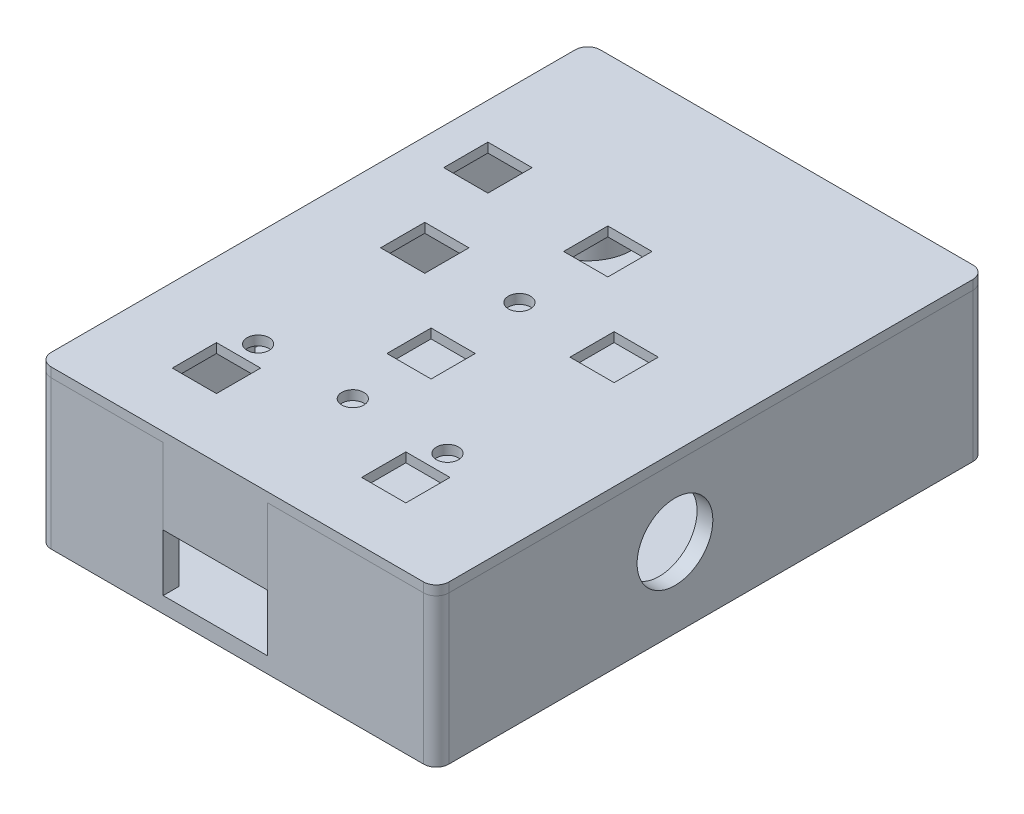
SolidWorks part; units mm, degrees
ref_plane "前视基准面" through (0, 0, 0) normal (0, 0, 1) x (1, 0, 0)
ref_plane "上视基准面" through (0, 0, 0) normal (0, 1, 0) x (1, 0, 0)
ref_plane "右视基准面" through (0, 0, 0) normal (1, 0, 0) x (0, 0, -1)
sketch "草图1" plane through (0, 0, 0) normal (0, 1, 0) x (1, 0, 0)
  line L0 (-11.76, -41) -> (-11.76, -43.5)
  line L1 (-26, 38) -> (26, 38) construction
  line L2 (-26, 38) -> (-26, -38) construction
  line L3 (-26, -38) -> (26, -38) construction
  line L4 (26, 38) -> (26, -38) construction
  line L5 (-26, 38) -> (26, -38) construction
  line L6 (-26, -38) -> (26, 38) construction
  line L7 (-29, 41) -> (29, 41)
  line L8 (-29, 41) -> (-29, -41)
  line L9 (-29, -41) -> (29, -41)
  line L10 (29, 41) -> (29, -41)
  line L11 (-29, 41) -> (29, -41) construction
  line L12 (-29, -41) -> (29, 41) construction
  line L13 (-29.5, 43.5) -> (29.5, 43.5)
  line L14 (-31.5, 41.5) -> (-31.5, -41.5)
  line L15 (-29.5, -43.5) -> (29.5, -43.5)
  line L16 (31.5, 41.5) -> (31.5, -41.5)
  line L17 (-31.5, 43.5) -> (31.5, -43.5) construction
  line L18 (-31.5, -43.5) -> (31.5, 43.5) construction
  line L19 (4.74, -41) -> (4.74, -43.5)
  line L20 (23.65, 43.5) -> (23.65, 41)
  line L21 (-23.35, 43.5) -> (-23.35, 41)
  line L22 (-16.35, 43.5) -> (-16.35, 41)
  line L23 (-31.5, 0.32) -> (-29, 0.32)
  line L24 (-31.5, -11.68) -> (-29, -11.68)
  circle A0 centre (-26, 38) radius 0.75
  circle A1 centre (26, 38) radius 0.75
  circle A2 centre (26, -38) radius 0.75
  circle A3 centre (-26, -38) radius 0.75
  arc A4 (-29.5, -43.5) -> (-31.5, -41.5) centre (-29.5, -41.5) cw
  arc A5 (31.5, -41.5) -> (29.5, -43.5) centre (29.5, -41.5) cw
  arc A6 (29.5, 43.5) -> (31.5, 41.5) centre (29.5, 41.5) cw
  arc A7 (-29.5, 43.5) -> (-31.5, 41.5) centre (-29.5, 41.5) ccw
  arc A8 (-29, -34) -> (-22, -41) centre (-29, -41) cw
  arc A9 (22, -41) -> (29, -34) centre (29, -41) cw
  arc A10 (29, 34) -> (22, 41) centre (29, 41) cw
  arc A11 (-22, 41) -> (-29, 34) centre (-29, 41) cw
  point P0 (0, 0)
  point P10 (0, 0)
  point P15 (0, 0)
  dimension "D3" = 1.5
  dimension "D8" = 2
  dimension "D11" = 7
  dimension "D1" = 76
  dimension "D2" = 52
  dimension "D4" = 3
  dimension "D5" = 3
  dimension "D6" = 2.5
  dimension "D7" = 2.5
  dimension "D9" = 14.24
  dimension "D10" = 16.5
  dimension "D12" = 2.35
  dimension "D13" = 7
  dimension "D14" = 40
  dimension "D15" = 12
  dimension "D16" = 26.32
extrude "凸台-拉伸1" add sketch "草图1" against normal blind 2.5 contours L14 A4 L15 A5 L16 A6 L13 A7
extrude "凸台-拉伸2" add sketch "草图1<4>" along normal blind 3 contours A11 L7 L8 A0 | A10 L10 L7 A1 | A9 L9 L10 A2 | A8 L8 L9 A3 region at (-25.5, 0, 40.901) region at (24.1203, 0, 36.1203) region at (24.1203, 0, -36.1203) region at (-28.901, 0, -37.5)
sketch "草图1<4>" plane through (0, 0, 0) normal (0, 1, 0) x (1, 0, 0) same geometry as "草图1"
extrude "凸台-拉伸4" add sketch "草图1<5>" along normal blind 4.6 separate body contours L13 L21 L7 L20 region at (3.65, 0, -42.25)
sketch "草图1<5>" plane through (0, 0, 0) normal (0, 1, 0) x (1, 0, 0) same geometry as "草图1"
extrude "凸台-拉伸5" add sketch "草图1<6>" along normal blind 21 contours L13 A7 L14 A4 L15 L0 L9 L8 L7 L21 | A6 L13 L20 L7 L10 L9 L19 L15 A5 L16 | L13 A7 L14 L23 L8 L7 L21 region at (-12.1345, 0, 42.25) region at (13.37, 0, 41.9102) region at (-29.7695, 0, -24.1304)
sketch "草图1<6>" plane through (0, 0, 0) normal (0, 1, 0) x (1, 0, 0) same geometry as "草图1"
extrude "凸台-拉伸6" add sketch "草图1<7>" along normal blind 9.4 contours L22 L13 L21 L7 region at (-19.85, 0, -42.25)
sketch "草图1<7>" plane through (0, 0, 0) normal (0, 1, 0) x (1, 0, 0) same geometry as "草图1"
sketch "草图2" plane through (0, 0, -43.5) normal (0, 0, -1) x (-1, 0, 0)
  line L0 (23.35, 9.4) -> (16.35, 9.4) construction
  circle A0 centre (19.85, 9.4) radius 3.5
extrude "切除-拉伸1" cut sketch "草图2" against normal up to next
sketch "草图3" plane through (31.5, 0, 0) normal (1, 0, 0) x (0, 0, -1)
  line L2 (-38, 3) -> (-38, 0) construction
  line L3 (34, 0) -> (-34, 0) construction
  circle A0 centre (-5.68, 10.1) radius 6
  dimension "D2" = 12
  dimension "D1" = 32.32
  dimension "D3" = 10.1
extrude "切除-拉伸2" cut sketch "草图3" against normal up to next
extrude "凸台-拉伸11" add sketch "草图1<8>" along normal blind 7 contours L14 L24 L8 L23 region at (-30.25, 0, 5.68)
sketch "草图1<8>" plane through (0, 0, 0) normal (0, 1, 0) x (1, 0, 0) same geometry as "草图1"
sketch "草图4" plane through (0, 21, 0) normal (0, 1, 0) x (1, 0, 0)
  line L0 (-11.76, -41) -> (-11.76, -43.5)
  line L1 (-26, 38) -> (26, 38) construction
  line L2 (-26, 38) -> (-26, -38) construction
  line L3 (-26, -38) -> (26, -38) construction
  line L4 (26, 38) -> (26, -38) construction
  line L5 (-26, 38) -> (26, -38) construction
  line L6 (-26, -38) -> (26, 38) construction
  line L7 (-29, 41) -> (29, 41)
  line L8 (-29, 41) -> (-29, -41)
  line L9 (-29, -41) -> (29, -41)
  line L10 (29, 41) -> (29, -41)
  line L11 (-29, 41) -> (29, -41) construction
  line L12 (-29, -41) -> (29, 41) construction
  line L13 (-29.5, 43.5) -> (29.5, 43.5)
  line L14 (-31.5, 41.5) -> (-31.5, -41.5)
  line L15 (-29.5, -43.5) -> (29.5, -43.5)
  line L16 (31.5, 41.5) -> (31.5, -41.5)
  line L17 (-31.5, 43.5) -> (31.5, -43.5) construction
  line L18 (-31.5, -43.5) -> (31.5, 43.5) construction
  line L19 (4.74, -41) -> (4.74, -43.5)
  line L20 (23.65, 43.5) -> (23.65, 41)
  line L21 (-23.35, 43.5) -> (-23.35, 41)
  line L22 (-16.35, 43.5) -> (-16.35, 41)
  line L23 (-31.5, 0.32) -> (-29, 0.32)
  line L24 (-31.5, -11.68) -> (-29, -11.68)
  line L25 (10.25, 5.93) -> (17.25, 5.93)
  line L26 (-16.35, 43.5) -> (-23.35, 43.5) construction
  line L27 (-11.76, -41) -> (-11.76, -43.5) construction
  line L28 (4.74, -41) -> (4.74, -43.5) construction
  line L29 (-29, -41) -> (-11.76, -41) construction
  line L30 (29, 41) -> (29, -41) construction
  line L31 (31.5, 41.5) -> (31.5, -41.5) construction
  line L32 (-23.35, 43.5) -> (-23.35, 41) construction
  line L33 (-16.35, 43.5) -> (-16.35, 41) construction
  line L34 (23.65, 43.5) -> (23.65, 41) construction
  line L35 (-4.75, 19.93) -> (2.25, 19.93)
  line L36 (-4.75, 19.93) -> (-4.75, 12.93)
  line L37 (-4.75, 12.93) -> (2.25, 12.93)
  line L38 (2.25, 19.93) -> (2.25, 12.93)
  line L39 (-4.75, 19.93) -> (2.25, 12.93) construction
  line L40 (-4.75, 12.93) -> (2.25, 19.93) construction
  line L41 (10.25, 5.93) -> (10.25, -1.07)
  line L42 (10.25, -1.07) -> (17.25, -1.07)
  line L43 (17.25, 5.93) -> (17.25, -1.07)
  line L44 (10.25, 5.93) -> (17.25, -1.07) construction
  line L45 (10.25, -1.07) -> (17.25, 5.93) construction
  line L46 (-19.75, 5.93) -> (-12.75, 5.93)
  line L47 (-19.75, 5.93) -> (-19.75, -1.07)
  line L48 (-19.75, -1.07) -> (-12.75, -1.07)
  line L49 (-12.75, 5.93) -> (-12.75, -1.07)
  line L50 (-19.75, 5.93) -> (-12.75, -1.07) construction
  line L51 (-19.75, -1.07) -> (-12.75, 5.93) construction
  line L52 (-4.75, -8.07) -> (2.25, -8.07)
  line L53 (-4.75, -8.07) -> (-4.75, -15.07)
  line L54 (-4.75, -15.07) -> (2.25, -15.07)
  line L55 (2.25, -8.07) -> (2.25, -15.07)
  line L56 (-4.75, -8.07) -> (2.25, -15.07) construction
  line L57 (-4.75, -15.07) -> (2.25, -8.07) construction
  line L58 (-19.75, -27.07) -> (-12.75, -27.07)
  line L59 (-19.75, -27.07) -> (-19.75, -34.07)
  line L60 (-19.75, -34.07) -> (-12.75, -34.07)
  line L61 (-12.75, -27.07) -> (-12.75, -34.07)
  line L62 (-19.75, -27.07) -> (-12.75, -34.07) construction
  line L63 (-19.75, -34.07) -> (-12.75, -27.07) construction
  line L64 (10.25, -27.07) -> (17.25, -27.07)
  line L65 (10.25, -27.07) -> (10.25, -34.07)
  line L66 (10.25, -34.07) -> (17.25, -34.07)
  line L67 (17.25, -27.07) -> (17.25, -34.07)
  line L68 (10.25, -27.07) -> (17.25, -34.07) construction
  line L69 (10.25, -34.07) -> (17.25, -27.07) construction
  line L70 (-16.25, 2.43) -> (13.75, 2.43) construction
  line L71 (-1.25, 2.43) -> (-1.25, 16.43) construction
  line L72 (-16.25, -30.57) -> (13.75, -30.57) construction
  line L73 (-1.25, -30.57) -> (-1.25, -11.57) construction
  line L74 (-1.25, 2.43) -> (-1.25, -11.57) construction
  line L75 (-16.25, -23.97) -> (-16.25, -30.57) construction
  line L76 (13.75, -23.97) -> (13.75, -30.57) construction
  line L77 (-16.25, -23.97) -> (13.75, -23.97) construction
  line L78 (-25.75, 21.93) -> (-18.75, 21.93)
  line L79 (-25.75, 21.93) -> (-25.75, 14.93)
  line L80 (-25.75, 14.93) -> (-18.75, 14.93)
  line L81 (-18.75, 21.93) -> (-18.75, 14.93)
  line L82 (-25.75, 21.93) -> (-18.75, 14.93) construction
  line L83 (-25.75, 14.93) -> (-18.75, 21.93) construction
  line L84 (-29, -36.0503) -> (-24.0503, -36.0503)
  line L85 (24.0503, -36.0503) -> (29, -36.0503)
  line L86 (-24.0503, 36.0503) -> (-29, 36.0503)
  line L87 (24.0503, 36.0503) -> (29, 36.0503)
  circle A0 centre (-26, 38) radius 0.75
  circle A1 centre (26, 38) radius 0.75
  circle A2 centre (26, -38) radius 0.75
  circle A3 centre (-26, -38) radius 0.75
  arc A4 (-29.5, -43.5) -> (-31.5, -41.5) centre (-29.5, -41.5) cw
  arc A5 (31.5, -41.5) -> (29.5, -43.5) centre (29.5, -41.5) cw
  arc A6 (29.5, 43.5) -> (31.5, 41.5) centre (29.5, 41.5) cw
  arc A7 (-29.5, 43.5) -> (-31.5, 41.5) centre (-29.5, 41.5) ccw
  arc A8 (-29, -34) -> (-22, -41) centre (-29, -41) cw
  arc A9 (22, -41) -> (29, -34) centre (29, -41) cw
  arc A10 (29, 34) -> (22, 41) centre (29, 41) cw
  arc A11 (-22, 41) -> (-29, 34) centre (-29, 41) cw
  circle A12 centre (-26, 38) radius 0.75 construction
  arc A13 (-29, 34) -> (-22, 41) centre (-29, 41) ccw construction
  arc A14 (-29.5, 43.5) -> (-31.5, 41.5) centre (-29.5, 41.5) ccw construction
  circle A15 centre (-1.25, 2.43) radius 1.75
  circle A16 centre (-16.25, -23.97) radius 1.75
  circle A17 centre (-1.25, -23.97) radius 1.75
  circle A18 centre (13.75, -23.97) radius 1.75
  point P0 (0, 0)
  point P9 (0, 0)
  point P14 (0, 0)
  point P85 (-1.25, 16.43)
  point P90 (13.75, 2.43)
  point P95 (-16.25, 2.43)
  point P100 (-1.25, -11.57)
  point P105 (-16.25, -30.57)
  point P110 (13.75, -30.57)
  point P130 (-22.25, 18.43)
  line M14 (-31.5, -11.68) -> (-31.5, -41.5)
  arc M15 (-31.5, -41.5) -> (-29.5, -43.5) centre (-29.5, -41.5) ccw
  line M16 (-29.5, -43.5) -> (-11.76, -43.5)
  line M17 (-11.76, -43.5) -> (-11.76, -41)
  line M18 (-11.76, -41) -> (-29, -41)
  line M19 (-29, -41) -> (-29, -11.68)
  line M58 (-29, -11.68) -> (-31.5, -11.68)
  dimension "D4" = 3.5
  dimension "D1" = 7
  dimension "D2" = 30
  dimension "D3" = 14
  dimension "D5" = 19
  dimension "D6" = 7.43
  dimension "D7" = 6.6
  dimension "D8" = 16
  dimension "D9" = 6
  dimension "D10" = 24.75
extrude "凸台-拉伸7" add sketch "草图4" along normal blind 1.5 separate body contours L7 A11 L8 A8 L9 A9 L10 A10 A18 A17 A16 A15 L35 L38 L37 L36 L25 L43 L42 L41 L46 L49 L48 L47 L52 L55 L54 L53 L58 L61 L60 L59 L64 L67 L66 L65 M18 | L23 L14 L8 M58 | L13 A7 L14 L23 L8 L7 L21 | L9 L8 M14 M15 M16 M17 M18 M19 M58 | A8 L9 A3 M19 | L19 L9 L15 M17 | A6 L13 L20 L7 L10 L9 L19 L15 A5 L16 | A9 L9 L10 A2 | A10 L10 L7 A1 | L13 L22 L7 L20 | A11 L7 L8 A0 | L22 L13 L21 L7 | A0 | A1 | A2 | A3 | A10 L10 L87 | A11 L86 L8 | A8 L8 L84 | A9 L85 L10 region at (-3.51, 21, 42.25) region at (-12.1345, 21, 42.25) region at (0.3568, 21, -0.5414) region at (-25.5, 21, 40.9143) region at (13.37, 21, 41.9102) region at (-27.1013, 21, 35.2189) region at (22.612, 21, 38.354) region at (27.1013, 21, 35.2189) region at (-30.25, 21, 5.68) region at (-29.7695, 21, -24.1304) region at (27.1013, 21, -35.2189) region at (-27.1013, 21, -35.2189) region at (26.5251, 21, -36.136) region at (3.65, 21, -42.25) region at (-28.9143, 21, -38.5251) region at (-19.85, 21, -42.25) region at (-26, 21, -38) region at (26, 21, -38) region at (26, 21, 38) region at (-26, 21, 38)
extrude "凸台-拉伸8" add sketch "草图4<4>" against normal blind 12 contours L19 L9 L15 M17 region at (-3.51, 21, 42.25)
sketch "草图4<4>" plane through (0, 21, 0) normal (0, 1, 0) x (1, 0, 0) same geometry as "草图4"
extrude "凸台-拉伸9" add sketch "草图4<5>" against normal blind 11.5 contours L22 L13 L7 region at (-19.85, 21, -42.25)
sketch "草图4<5>" plane through (0, 21, 0) normal (0, 1, 0) x (1, 0, 0) same geometry as "草图4"
sketch "草图5" plane through (0, 0, -43.5) normal (0, 0, -1) x (-1, 0, 0)
  line L0 (23.35, 9.5) -> (16.35, 9.5) construction
  circle A0 centre (19.85, 9.5) radius 3.5
  dimension "D1" = 7
extrude "切除-拉伸3" cut sketch "草图5" against normal up to next (2.5 mm away)
extrude "凸台-拉伸10" add sketch "草图4<6>" against normal blind 4.4 contours L13 L22 L7 L20 region at (3.65, 21, -42.25)
sketch "草图4<6>" plane through (0, 21, 0) normal (0, 1, 0) x (1, 0, 0) same geometry as "草图4"
extrude "凸台-拉伸12" add sketch "草图4<7>" against normal blind 8.6 contours L23 L14 L8 M58 region at (-30.25, 21, 5.68)
sketch "草图4<7>" plane through (0, 21, 0) normal (0, 1, 0) x (1, 0, 0) same geometry as "草图4"
extrude "凸台-拉伸13" add sketch "草图4<8>" against normal blind 4 contours A11 L7 L8 A0 | A10 L10 L7 A1 | A9 L9 L10 A2 | A8 L9 A3 M19 | A3 | A2 | A1 | A0 region at (-25.5, 21, 40.9143) region at (22.612, 21, 38.354) region at (26.5251, 21, -36.136) region at (-28.9143, 21, -38.5251) region at (-26, 21, -38) region at (26, 21, -38) region at (26, 21, 38) region at (-26, 21, 38)
sketch "草图4<8>" plane through (0, 21, 0) normal (0, 1, 0) x (1, 0, 0) same geometry as "草图4"
